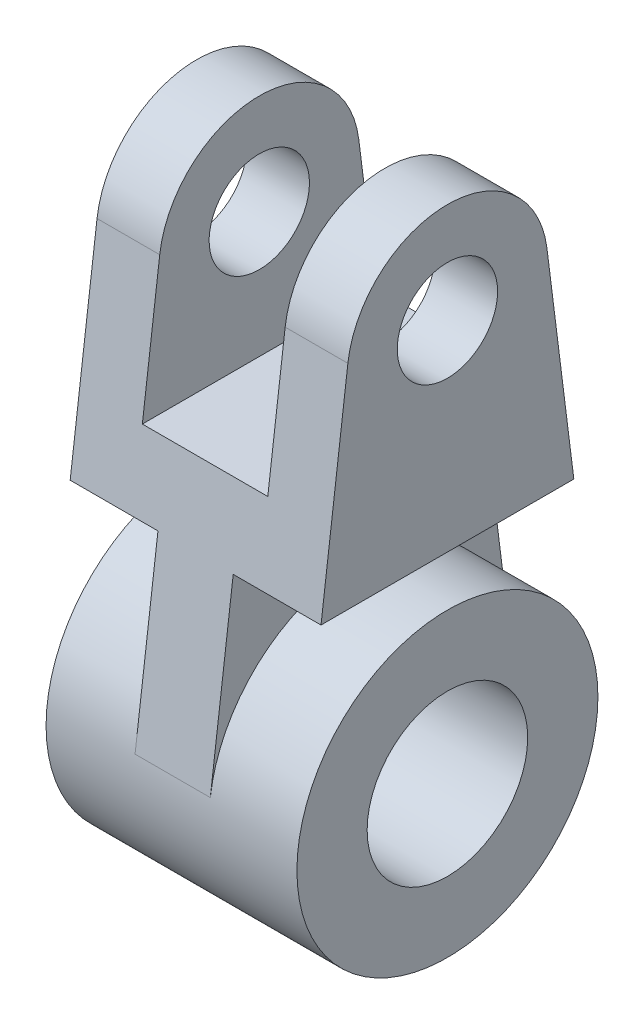
SolidWorks part; units mm, degrees
ref_plane "Front Plane" through (0, 0, 0) normal (0, 0, 1) x (1, 0, 0)
ref_plane "Top Plane" through (0, 0, 0) normal (0, 1, 0) x (1, 0, 0)
ref_plane "Right Plane" through (0, 0, 0) normal (1, 0, 0) x (0, 0, -1)
sketch "Sketch1" plane through (0, 0, 0) normal (1, 0, 0) x (0, 0, -1)
  circle A0 centre (0, 0) radius 30
  dimension "D1" = 60
extrude "Boss-Extrude1" add sketch "Sketch1" along normal mid plane 50
sketch "Sketch2" plane through (0, 0, 0) normal (1, 0, 0) x (0, 0, -1)
  circle A0 centre (0, 0) radius 16
  dimension "D1" = 32
extrude "Cut-Extrude1" cut sketch "Sketch2" against normal mid plane 50
sketch "Sketch3" plane through (0, 0, 0) normal (1, 0, 0) x (0, 0, -1)
  line L0 (0, 0) -> (0, 80) construction
  line L1 (-25.1976, 40) -> (25.1976, 40)
  line L2 (29.7647, 3.75) -> (19.8431, 82.5)
  line L4 (-19.8431, 82.5) -> (-29.7647, 3.75)
  arc A3 (19.8431, 82.5) -> (-19.8431, 82.5) centre (0, 80) ccw
  circle A4 centre (0, 0) radius 30
  circle A5 centre (0, 0) radius 30
  point P7 (0, 0)
  point P13 (0, 0)
  dimension "D3" = 20
  dimension "D2" = 80
  dimension "D4" = 60
  dimension "D1" = 0
extrude "Boss-Extrude3" add sketch "Sketch3" along normal mid plane 50 separate body contours L2 A3 L4 L1 region at (0, 66.7796, 0)
extrude "Boss-Extrude4" add sketch "Sketch3<3>" along normal mid plane 15 contours L0 A5 L2 L1 | A5 L0 L1 L4 region at (0, 31.1344, 15.9348) region at (0, 31.1344, -15.9348)
sketch "Sketch3<3>" plane through (0, 0, 0) normal (1, 0, 0) x (0, 0, -1) same geometry as "Sketch3"
sketch "Sketch4" plane through (25, 0, 0) normal (1, 0, 0) x (0, 0, -1)
  circle A0 centre (0, 80) radius 10
  dimension "D1" = 20
extrude "Cut-Extrude2" cut sketch "Sketch4" against normal through all
sketch "Sketch5" plane through (0, 0, 0) normal (0, 0, 1) x (1, 0, 0)
  line L0 (25, 100) -> (-25, 100) construction
  line L1 (12.5, 100) -> (-12.5, 100)
  line L2 (12.5, 100) -> (12.5, 55)
  line L3 (12.5, 55) -> (-12.5, 55)
  line L4 (-12.5, 100) -> (-12.5, 55)
  line L5 (25, 82.5) -> (25, 100) construction
  dimension "D1" = 45
  dimension "D2" = 25
  dimension "D3" = 12.5
extrude "Cut-Extrude3" cut sketch "Sketch5" against normal through all both and the other way through all
